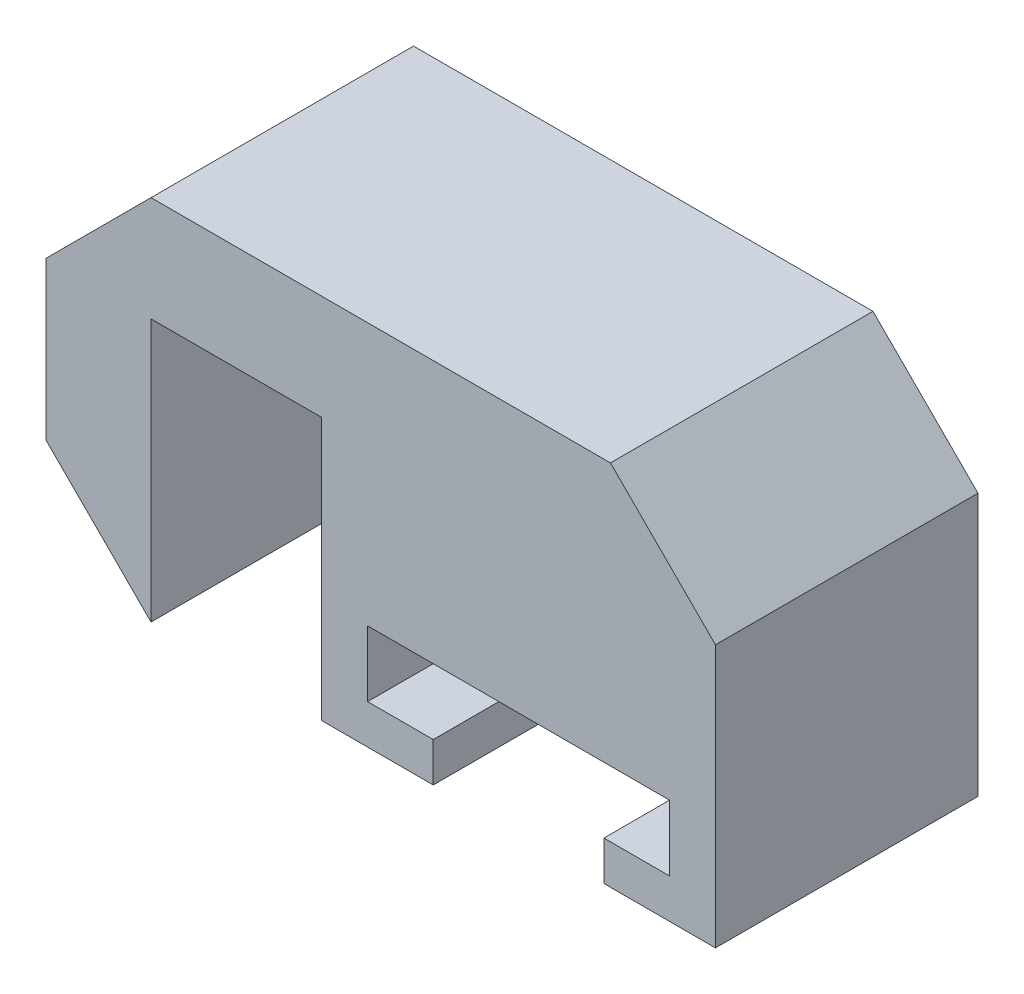
SolidWorks part; units mm, degrees
ref_plane "Front Plane" through (0, 0, 0) normal (0, 0, 1) x (1, 0, 0)
ref_plane "Top Plane" through (0, 0, 0) normal (0, 1, 0) x (1, 0, 0)
ref_plane "Right Plane" through (0, 0, 0) normal (1, 0, 0) x (0, 0, -1)
sketch "Sketch1" plane through (0, 0, 0) normal (0, 0, 1) x (1, 0, 0)
  line L0 (0, 0) -> (15, 0)
  line L1 (15, 0) -> (15, 14)
  line L2 (15, 14) -> (-10.5, 14)
  line L3 (-10.5, 14) -> (-10.5, 0)
  line L4 (-10.5, 0) -> (-6.5, 0)
  line L5 (-6.5, 0) -> (-6.5, 10)
  line L6 (-6.5, 10) -> (0, 10)
  line L7 (0, 10) -> (0, 0)
  dimension "D1" = 15
  dimension "D2" = 6.5
  dimension "D3" = 4
  dimension "D4" = 10
  dimension "D5" = 4
extrude "Boss-Extrude1" add sketch "Sketch1" along normal blind 10
chamfer "Chamfer1" distance 4 angle 45 3 edges at (-10.5, 14, 5) (15, 14, 5) (-10.5, 0, 5)
sketch "Sketch2" plane through (0, 0, 10) normal (0, 0, 1) x (1, 0, 0)
  line L0 (4.25, 0) -> (4.25, 1.5)
  line L1 (0, 0) -> (15, 0) construction
  line L2 (4.25, 1.5) -> (1.75, 1.5)
  line L3 (1.75, 1.5) -> (1.75, 4)
  line L4 (1.75, 4) -> (13.25, 4)
  line L5 (13.25, 4) -> (13.25, 1.5)
  line L6 (13.25, 1.5) -> (10.75, 1.5)
  line L7 (10.75, 1.5) -> (10.75, 0)
  line L8 (10.75, 0) -> (4.25, 0)
  line L9 (7.5, 4) -> (7.5, 0) construction
  dimension "D1" = 6.5
  dimension "D2" = 1.5
  dimension "D3" = 2.5
  dimension "D4" = 2.5
extrude "Cut-Extrude1" cut sketch "Sketch2" against normal through all
